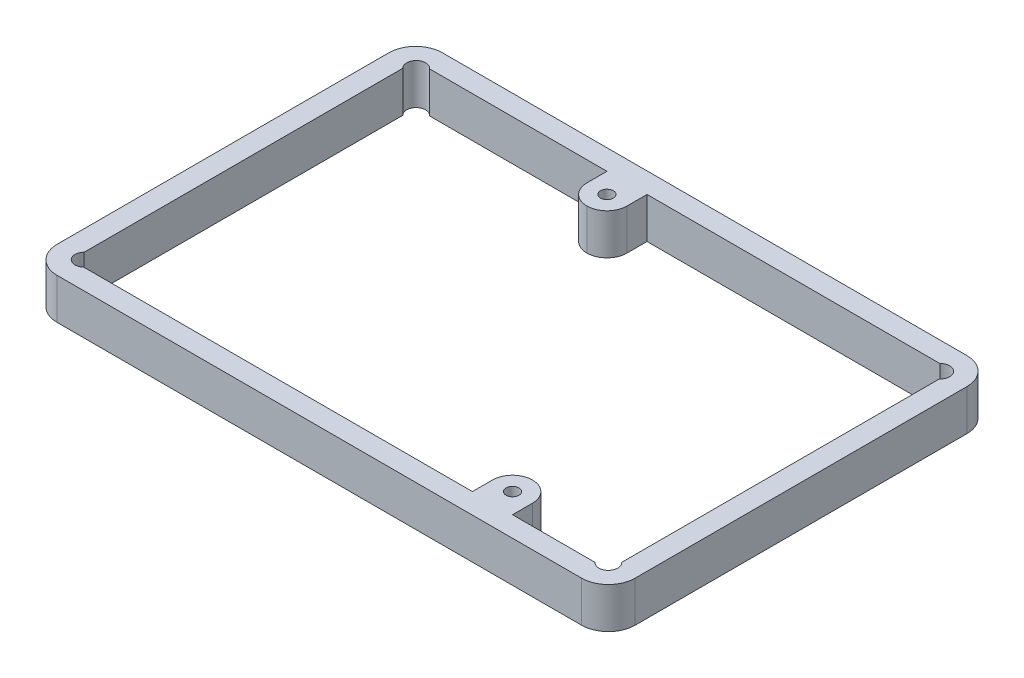
SolidWorks part; units mm, degrees
ref_plane "Front" through (0, 0, 0) normal (0, 0, 1) x (1, 0, 0)
ref_plane "Top" through (0, 0, 0) normal (0, 1, 0) x (1, 0, 0)
ref_plane "Right" through (0, 0, 0) normal (1, 0, 0) x (0, 0, -1)
sketch "Sketch1" plane through (0, 0, 0) normal (0, 1, 0) x (1, 0, 0)
  line L0 (-45, 0) -> (45, 0) construction
  line L1 (-45, 30) -> (45, 30) construction
  line L2 (-45, 30) -> (-45, -30) construction
  line L3 (-45, -30) -> (45, -30) construction
  line L4 (45, 30) -> (45, -30) construction
  line L5 (0, -30) -> (0, 30) construction
  line L6 (41.825, 26.825) -> (41.825, -26.825) construction
  line L7 (-41.825, -26.825) -> (41.825, -26.825) construction
  line L8 (-41.825, 26.825) -> (-41.825, -26.825) construction
  line L9 (-41.825, 26.825) -> (41.825, 26.825) construction
  line L10 (40.825, 25.825) -> (40.825, -25.825) construction
  line L11 (-40.825, -25.825) -> (40.825, -25.825) construction
  line L12 (-40.825, 25.825) -> (-40.825, -25.825) construction
  line L13 (-40.825, 25.825) -> (40.825, 25.825) construction
  line L14 (40.825, 21.65) -> (45, 21.65) construction
  line L15 (40.825, -21.65) -> (45, -21.65) construction
  line L16 (36.65, -25.825) -> (36.65, -30) construction
  line L17 (-36.65, -25.825) -> (-36.65, -30) construction
  line L18 (-40.825, -21.65) -> (-45, -21.65) construction
  line L19 (-36.65, 25.825) -> (-36.65, 30) construction
  line L20 (-40.825, 21.65) -> (-45, 21.65) construction
  line L21 (36.65, 25.825) -> (36.65, 30) construction
  line L22 (40.825, -25.825) -> (41.825, -25.825) construction
  circle A0 centre (-40.825, -25.825) radius 1 construction
  circle A1 centre (40.825, -25.825) radius 1 construction
  circle A2 centre (40.825, 25.825) radius 1 construction
  circle A3 centre (-40.825, 25.825) radius 1 construction
  circle A4 centre (40.825, -25.825) radius 4.175 construction
  circle A5 centre (40.825, 25.825) radius 4.175 construction
  circle A6 centre (-40.825, 25.825) radius 4.175 construction
  circle A7 centre (-40.825, -25.825) radius 4.175 construction
  dimension "D1" = 90
  dimension "D2" = 60
  dimension "D4" = 1
  dimension "D3" = 3.175
sketch "Sketch2" plane through (0, 0, 0) normal (0, 1, 0) x (1, 0, 0)
  line L0 (-45, 30) -> (-45, -30) construction
  line L1 (-45, -30) -> (45, -30) construction
  line L2 (45, 30) -> (45, -30) construction
  line L3 (-45, 30) -> (45, 30) construction
  line L12 (-41.825, -25.825) -> (-41.825, 25.825)
  line L13 (-40.825, 26.825) -> (40.825, 26.825)
  line L14 (41.825, 25.825) -> (41.825, -25.825)
  line L15 (40.825, -26.825) -> (-40.825, -26.825)
  line L16 (-45, 25.825) -> (-45, -25.825)
  line L17 (-40.825, -30) -> (40.825, -30)
  line L18 (45, 25.825) -> (45, -25.825)
  line L19 (-40.825, 30) -> (40.825, 30)
  circle A0 centre (40.825, 25.825) radius 4.175 construction
  circle A1 centre (40.825, 25.825) radius 1 construction
  circle A2 centre (-40.825, 25.825) radius 4.175 construction
  circle A3 centre (-40.825, 25.825) radius 1 construction
  arc A6 (45, 25.825) -> (40.825, 30) centre (40.825, 25.825) ccw
  arc A7 (41.825, 25.825) -> (40.825, 26.825) centre (40.825, 25.825) ccw
  arc A8 (-40.825, 30) -> (-45, 25.825) centre (-40.825, 25.825) ccw
  arc A9 (-40.825, 26.825) -> (-41.825, 25.825) centre (-40.825, 25.825) ccw
  circle A12 centre (-40.825, -25.825) radius 1 construction
  circle A13 centre (40.825, -25.825) radius 1 construction
  arc A14 (-41.825, -25.825) -> (-40.825, -26.825) centre (-40.825, -25.825) ccw
  arc A15 (40.825, -26.825) -> (41.825, -25.825) centre (40.825, -25.825) ccw
  arc A17 (-45, -25.825) -> (-40.825, -30) centre (-40.825, -25.825) ccw
  arc A18 (40.825, -30) -> (45, -25.825) centre (40.825, -25.825) ccw
extrude "Boss-Extrude3" add sketch "Sketch2" along normal blind 6.35
sketch "Sketch3" plane through (-7.8754, 0, 26.825) normal (0, 0, -1) x (-1, 0, 0)
  line L0 (32.9496, 6.35) -> (-48.7004, 6.35) construction
  line L1 (-34.7804, 6.35) -> (-28.5404, 6.35)
  line L2 (-34.7804, 6.35) -> (-34.7804, 0)
  line L3 (-34.7804, 0) -> (-28.5404, 0)
  line L4 (-28.5404, 6.35) -> (-28.5404, 0)
  line L6 (-48.7004, 0) -> (32.9496, 0) construction
  dimension "D1" = 6.24
  dimension "D2" = 13.92
extrude "Boss-Extrude4" add sketch "Sketch3" along normal blind 6.24
sketch "Sketch4" plane through (0, 0, 0) normal (0, -1, 0) x (1, 0, 0)
  line L0 (26.905, 26.825) -> (20.665, 20.585) construction
  circle A0 centre (23.785, 23.705) radius 1
fillet "Fillet1" radius 3.12 2 edges at (20.665, 3.175, 20.585) (26.905, 3.175, 20.585)
extrude "Cut-Extrude1" cut sketch "Sketch4" against normal through all
sketch "Sketch5" plane through (0, 0, 0) normal (0, -1, 0) x (1, 0, 0)
  circle A0 centre (-40.825, 25.7794) radius 1.4224 construction
  circle A1 centre (-40.825, 25.7794) radius 1.4224
  circle A2 centre (40.825, 25.825) radius 1.4732 construction
  circle A3 centre (40.8602, -25.8149) radius 1.4732 construction
  circle A4 centre (-40.7898, -25.8706) radius 1.4732 construction
  circle A5 centre (40.825, 25.825) radius 1.4732
  circle A6 centre (40.8602, -25.8149) radius 1.4732
  circle A7 centre (-40.7898, -25.8706) radius 1.4732
extrude "Cut-Extrude2" cut sketch "Sketch5" against normal through all
sketch "Sketch6" plane through (0, 0, -26.825) normal (0, 0, 1) x (1, 0, 0)
  line L0 (39.7879, 6.35) -> (-39.6675, 6.35) construction
  line L1 (-5.8039, 6.35) -> (-12.0439, 6.35)
  line L2 (-5.8039, 6.35) -> (-5.8039, 0)
  line L3 (-5.8039, 0) -> (-12.0439, 0)
  line L4 (-12.0439, 6.35) -> (-12.0439, 0)
  line L5 (39.7879, 0) -> (-39.6675, 0) construction
  dimension "D1" = 6.24
extrude "Boss-Extrude5" add sketch "Sketch6" along normal blind 6.24
sketch "Sketch7" plane through (0, 0, 0) normal (0, -1, 0) x (-1, 0, 0)
  line L0 (5.8039, 26.825) -> (12.0439, 20.585) construction
  line L1 (12.0439, 20.585) -> (12.0439, 26.825) construction
  circle A0 centre (8.9239, 23.705) radius 1
  dimension "D1" = 2
extrude "Cut-Extrude3" cut sketch "Sketch7" against normal through all
fillet "Fillet3" radius 3.12 2 edges at (-5.8039, 3.175, -20.585) (-12.0439, 3.175, -20.585)
